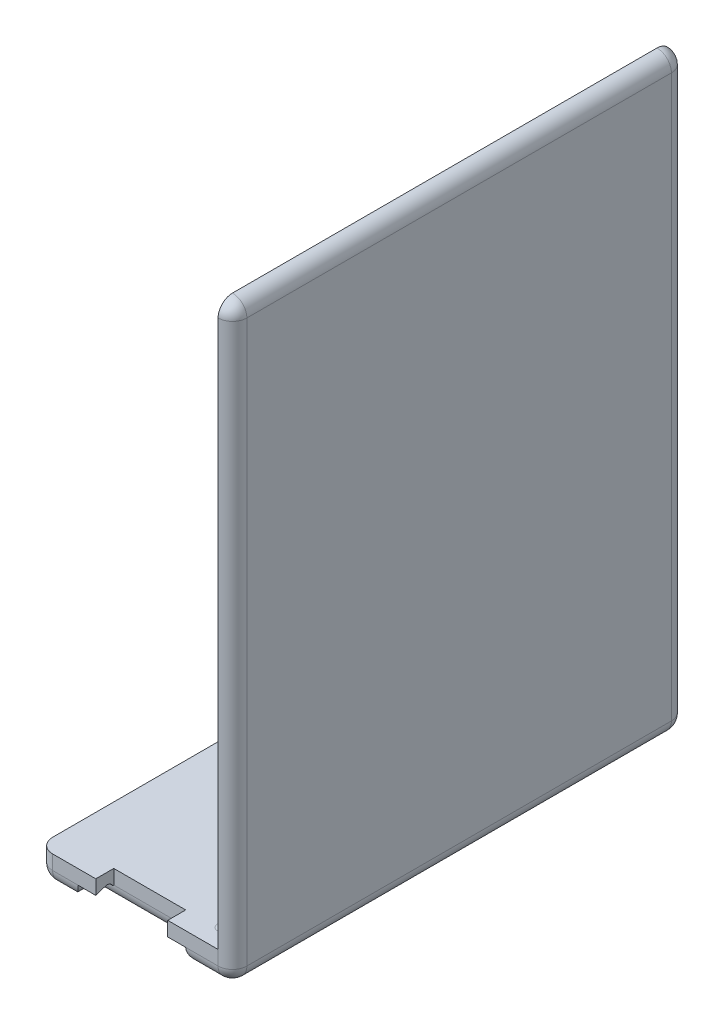
SolidWorks part; units mm, degrees
note: The reader was unsure of these and kept them because the rebuilt part matched: shared geometry of "Sketch6<3>".
ref_plane "Front Plane" through (0, 0, 0) normal (0, 0, 1) x (1, 0, 0)
ref_plane "Top Plane" through (0, 0, 0) normal (0, 1, 0) x (1, 0, 0)
ref_plane "Right Plane" through (0, 0, 0) normal (1, 0, 0) x (0, 0, -1)
sketch "Sketch1" plane through (0, 0, 0) normal (0, 1, 0) x (1, 0, 0)
  line L1 (0, 0) -> (-25, 0)
  line L2 (0, 0) -> (0, -63)
  line L3 (0, -63) -> (-25, -63)
  line L4 (-25, 0) -> (-25, -63)
  dimension "D1" = 63
  dimension "D2" = 25
extrude "Boss-Extrude1" add sketch "Sketch1" along normal blind 4
sketch "Sketch3" plane through (0, 0, 0) normal (1, 0, 0) x (0, 0, -1)
  line L1 (-63, 0) -> (0, 0)
  line L2 (-63, 0) -> (-63, 4)
  line L3 (-63, 4) -> (0, 4)
  line L4 (0, 0) -> (0, 4)
extrude "Boss-Extrude2" add sketch "Sketch3" along normal blind 2
sketch "Sketch4" plane through (0, 4, 0) normal (0, 1, 0) x (1, 0, 0)
  line L1 (2, -63) -> (0, -63)
  line L2 (2, -63) -> (2, 0)
  line L3 (2, 0) -> (0, 0)
  line L4 (0, -63) -> (0, 0)
extrude "Boss-Extrude3" add sketch "Sketch4" along normal blind 78
sketch "Sketch6" plane through (0, 0, 0) normal (0, -1, 0) x (1, 0, 0)
  line L0 (-25, 63) -> (2, 63) construction
  line L1 (-7, 63) -> (-17, 63)
  line L2 (-7, 63) -> (-7, 60.5)
  line L3 (-7, 60.5) -> (-17, 60.5)
  line L4 (-17, 63) -> (-17, 60.5)
  line L5 (2, 0) -> (-25, 0) construction
  line L6 (-7, 0) -> (-17, 0)
  line L7 (-7, 0) -> (-7, 2.5)
  line L8 (-7, 2.5) -> (-17, 2.5)
  line L9 (-17, 0) -> (-17, 2.5)
  line L10 (-25, 0) -> (-25, 63) construction
  dimension "D1" = 2.5
  dimension "D2" = 2.5
  dimension "D3" = 10
  dimension "D4" = 10
  dimension "D5" = 8
  dimension "D6" = 8
extrude "Cut-Extrude1" cut sketch "Sketch6" against normal through all contours L8 L9 L6 L7
extrude "Cut-Extrude2" cut sketch "Sketch6<3>" against normal blind 80 contours L3 L4 L1 L2
sketch "Sketch6<3>" plane through (0, 0, 0) normal (0, -1, 0) x (1, 0, 0) same geometry as "Sketch6"
sketch "Sketch8" plane through (0, 0, 63) normal (0, 0, 1) x (1, 0, 0)
  line L0 (-7, 0) -> (2, 0) construction
  line L1 (-4.5, 0) -> (-19.5, 0)
  line L2 (-4.5, 0) -> (-4.5, 2)
  line L3 (-4.5, 2) -> (-19.5, 2)
  line L4 (-19.5, 0) -> (-19.5, 2)
  line L5 (-25, 4) -> (-25, 0) construction
  dimension "D1" = 2
  dimension "D2" = 15
  dimension "D3" = 5.5
extrude "Cut-Extrude3" cut sketch "Sketch8" against normal blind 2.5
sketch "Sketch9" plane through (-4.5, 0, 0) normal (-1, 0, 0) x (0, 0, 1)
  line L0 (63, 0) -> (63, 2) construction
  line L1 (60.5, 2) -> (63, 2) construction
  line L2 (61.5, 2.5) -> (63, 2)
  line L3 (63, 2) -> (61.5, 2)
  line L4 (61.5, 2) -> (61.5, 2.5)
  circle A0 centre (61.5, 1.5) radius 1
  line M3 (63, 2) -> (60.5, 2)
  dimension "D1" = 2
  dimension "D2" = 1.5
  dimension "D3" = 0.5
extrude "Cut-Extrude5" cut sketch "Sketch9" along a picked direction on the side of the normal blind 15 contours A0 L3 M3 | L4 A0 M3
sketch "Sketch10" plane through (0, 0, 0) normal (0, -1, 0) x (1, 0, 0)
  line L0 (2, 31.5) -> (-25, 31.5) construction
  line L1 (2, 63) -> (2, 0) construction
  line L2 (-25, 0) -> (-25, 63) construction
  line L3 (-25, 31.5) -> (2, 31.5) construction
sketch "Sketch11" plane through (0, 0, 0) normal (0, 0, -1) x (-1, 0, 0)
  line L0 (-2, 0) -> (7, 0) construction
  line L1 (4.5, 0) -> (19.5, 0)
  line L2 (4.5, 0) -> (4.5, 2)
  line L3 (4.5, 2) -> (19.5, 2)
  line L4 (19.5, 0) -> (19.5, 2)
  line L5 (25, 4) -> (25, 0) construction
  dimension "D1" = 2
  dimension "D2" = 15
  dimension "D3" = 5.5
extrude "Cut-Extrude6" cut sketch "Sketch11" against normal blind 3 contours L2 L3 L4 L1
sketch "Sketch12" plane through (-4.5, 0, 0) normal (-1, 0, 0) x (0, 0, 1)
  line L0 (0, 0) -> (0, 2) construction
  line L1 (3, 2) -> (0, 2) construction
  line L2 (1.9, 2.5) -> (0, 2)
  line L3 (0, 2) -> (1.9, 2)
  line L4 (1.9, 2) -> (1.9, 2.5)
  circle A0 centre (1.9, 1.5) radius 1
  line M4 (3, 2) -> (0, 2)
  dimension "D1" = 2
  dimension "D2" = 1.9
  dimension "D3" = 0.5
extrude "Cut-Extrude7" cut sketch "Sketch12" along normal blind 15 contours A0 M4 | A0 L4 M4
fillet "Fillet6" radius 2 12 edges at (-19.5, 0, 1.5) (-22.25, 0, 0) (-25, 0, 31.5) (-22.25, 0, 63) (-19.5, 0, 61.75) (-12, 0, 60.5) (-4.5, 0, 61.75) (-1.25, 0, 63) (2, 0, 31.5) (-1.25, 0, 0) (-4.5, 0, 1.5) (-12, 0, 3)
fillet "Fillet7" radius 2 4 edges at (-24.4142, 0.5858, 0.5858) (-24.4142, 0.5858, 62.4142) (-25, 3, 0) (-25, 3, 63)
sketch "Sketch13" plane through (0, 4, 0) normal (0, 1, 0) x (1, 0, 0)
  line L6 (0, -4.25) -> (-1.5, -4.25)
  line L7 (0, 0) -> (0, -63) construction
  line L8 (-1.5, -4.25) -> (-1.5, -2.6)
  line L9 (-1.5, -2.6) -> (-2.7, -2.6)
  line L10 (-2.7, -2.6) -> (-2.7, -5.6)
  line L11 (-2.7, -5.6) -> (0, -5.6)
  line L12 (0, 0) -> (-7, 0) construction
  line L13 (0, -4.25) -> (0, -5.6)
  line L14 (0, -31.5) -> (-25.0562, -31.5) construction
  line L15 (-1.5, -60.4) -> (-2.7, -60.4)
  line L16 (-2.7, -60.4) -> (-2.7, -57.4)
  line L17 (-2.7, -57.4) -> (0, -57.4)
  line L18 (0, -58.75) -> (0, -57.4)
  line L19 (0, -58.75) -> (-1.5, -58.75)
  line L20 (-1.5, -58.75) -> (-1.5, -60.4)
  dimension "D1" = 1.5
  dimension "D2" = 1.2
  dimension "D3" = 2.6
  dimension "D4" = 3
  dimension "D5" = 1.35
extrude "Boss-Extrude4" add sketch "Sketch13" along normal blind 70
fillet "Fillet8" radius 0.4 24 edges at (-1.5, 4, 3.425) (0, 74, 4.925) (0, 74, 58.075) (-1.5, 4, 59.575) (-1.5, 39, 2.6) (-2.1, 74, 2.6) (-2.1, 4, 2.6) (-2.7, 39, 2.6) (-2.7, 74, 4.1) (-2.7, 4, 4.1) (-2.7, 39, 5.6) (-1.35, 74, 5.6) (0, 39, 5.6) (-1.35, 4, 5.6) (0, 39, 57.4) (-1.35, 74, 57.4) (-1.35, 4, 57.4) (-2.7, 39, 57.4) (-2.7, 74, 58.9) (-2.7, 4, 58.9) (-2.7, 39, 60.4) (-2.1, 74, 60.4) (-1.5, 39, 60.4) (-2.1, 4, 60.4)
fillet "Fillet9" radius 2 5 edges at (1.4142, 0.5858, 0.5858) (1.4142, 0.5858, 62.4142) (2, 82, 31.5) (2, 42, 0) (2, 42, 63)
sketch "Sketch14" plane through (0, 0, 0) normal (0, -1, 0) x (-1, 0, 0)
  line L0 (12, -58.5) -> (12, -5) construction
  line L1 (2.5, -58.5) -> (21.5, -58.5) construction
  line L2 (21.5, -5) -> (2.5, -5) construction
  text T0 "ECG\r\n" font "Century Gothic" height in points 36
extrude "Cut-Extrude8" cut sketch "Sketch14" against normal blind 2
